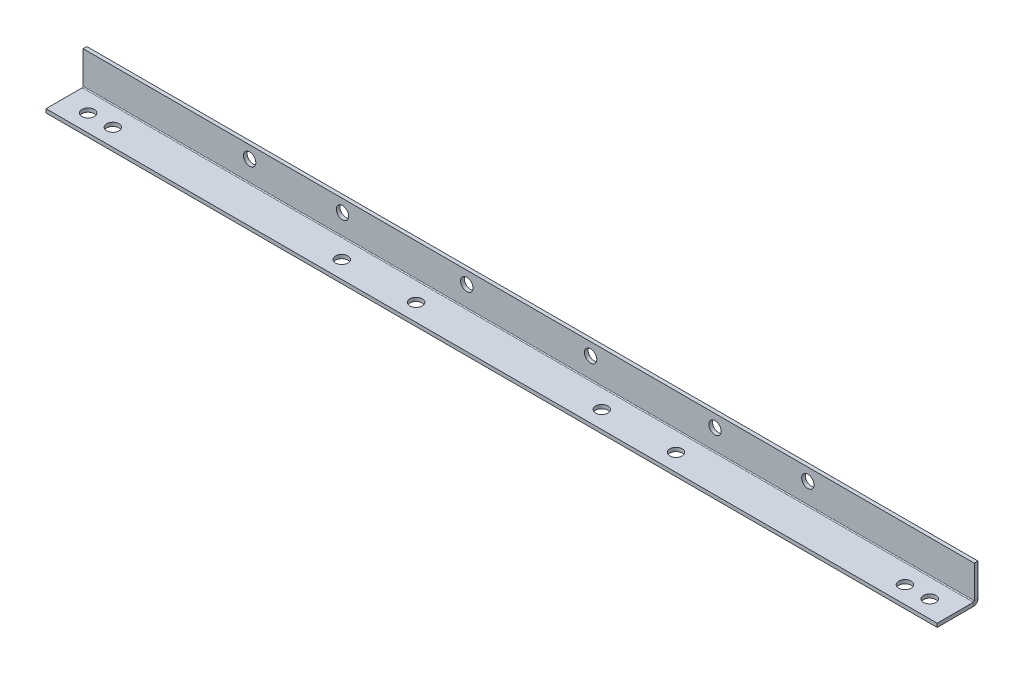
SolidWorks part; units mm, degrees
note: The reader was unsure of these and kept them because the rebuilt part matched: thickness of "Base-Flange1", "Edge-Flange1", "Sheet-Metal9", "Sheet-Metal10", "Sheet-Metal12", "Sheet-Metal13", "Sheet-Metal14", "Sheet-Metal15"; flange length of "Edge-Flange1".
material "6063-O"
ref_plane "Front Plane" through (0, 0, 0) normal (0, 0, 1) x (1, 0, 0)
ref_plane "Top Plane" through (0, 0, 0) normal (0, 1, 0) x (1, 0, 0)
ref_plane "Right Plane" through (0, 0, 0) normal (1, 0, 0) x (0, 0, -1)
sketch "Sketch2" plane through (0, 0, 0) normal (0, 1, 0) x (1, 0, 0)
  line L1 (-33.75, -275) -> (33.75, -275)
  line L2 (-33.75, -275) -> (-33.75, 275)
  line L3 (-33.75, 275) -> (33.75, 275)
  line L4 (33.75, -275) -> (33.75, 275)
  line L5 (-33.75, -275) -> (33.75, 275) construction
  line L6 (-33.75, 275) -> (33.75, -275) construction
  point P0 (0, 0)
sketch "Sketch3" plane through (0, 0, 0) normal (0, 1, 0) x (1, 0, 0)
  line L1 (-360, -15) -> (360, -15)
  line L2 (-360, -15) -> (-360, 15)
  line L3 (-360, 15) -> (360, 15)
  line L4 (360, -15) -> (360, 15)
  line L5 (-360, -15) -> (360, 15) construction
  line L6 (-360, 15) -> (360, -15) construction
  point P0 (0, 0)
  dimension "D1" = 720
  dimension "D2" = 30
base flange "Base-Flange1" sketch "Sketch3" thickness 3 reverse thickness direction no parameters "D1"=0.7366
edge flange "Edge-Flange1" sketch "Sketch8" flange angle 90 flange length 30 flange position material outside bend radius 0.7366 thickness 3 relief rectangular parameters "D6"=10
sketch "Sketch8" plane through (0, 0, -15) normal (0, 0, -1) x (-1, 0, 0)
  line L2 (-360, 0) -> (-360, 27)
  line L3 (-360, 27) -> (360, 27)
  line L4 (360, 27) -> (360, 0)
  line L11 (-360, 0) -> (360, 0) construction
  line L12 (-360, 0) -> (360, 0)
bend "EdgeBend1" bend radius 0.7366 bend angle 90 parameters "D5"=1
sketch "Sketch10" plane through (0, 0, 0) normal (0, 1, 0) x (1, 0, 0)
  line L0 (-360, 14.2634) -> (-360, -15) construction
  line L1 (-360, -15) -> (360, -15) construction
  circle A0 centre (-340, -1) radius 5
  circle A1 centre (-320, -1) radius 5
  dimension "D1" = 10
  dimension "D2" = 10
  dimension "D3" = 20
  dimension "D4" = 20
  dimension "D5" = 14
extrude "Cut-Extrude2" cut sketch "Sketch10" against normal blind 10 normal cut yes
mirror "Mirror1" about plane through (0, 0, 0) normal (1, 0, 0) of "Cut-Extrude2"
sketch "Sketch11" plane through (0, 0, -15) normal (0, 0, 1) x (1, 0, 0)
  line L0 (360, 27) -> (360, 0.7366) construction
  line L1 (-360, 0.7366) -> (-360, 27) construction
  line L2 (-360, 27) -> (360, 27) construction
  circle A0 centre (225.5, 17) radius 5
  circle A1 centre (-225.5, 17) radius 5
  circle A2 centre (-150.5, 17) radius 5
  circle A3 centre (150.5, 17) radius 5
  circle A4 centre (50, 17) radius 5
  circle A5 centre (-50, 17) radius 5
  point P18 (0, 27)
  dimension "D1" = 134.5
  dimension "D2" = 134.5
  dimension "D3" = 10
  dimension "D4" = 10
  dimension "D5" = 10
  dimension "D6" = 10
  dimension "D7" = 10
  dimension "D8" = 10
  dimension "D9" = 75
  dimension "D10" = 75
  dimension "D11" = 50
  dimension "D12" = 50
  dimension "D13" = 10
  dimension "D14" = 10
extrude "Cut-Extrude3" cut sketch "Sketch11" against normal blind 10 normal cut yes
sketch "Sketch12" plane through (0, 0, 0) normal (0, 1, 0) x (1, 0, 0)
  line L0 (-360, 18) -> (360, 18) construction
  circle A0 centre (-75, -1) radius 5
  circle A1 centre (75, -1) radius 5
  circle A2 centre (135, -1) radius 5
  circle A3 centre (-135, -1) radius 5
  point P10 (0, 18)
  dimension "D1" = 150
  dimension "D2" = 60
  dimension "D3" = 60
  dimension "D4" = 75
  dimension "D5" = 10
  dimension "D6" = 10
  dimension "D7" = 10
  dimension "D8" = 10
  dimension "D12" = 0
extrude "Cut-Extrude4" cut sketch "Sketch12" against normal blind 10 normal cut yes
sketch "Bend-Lines1" [suppressed] plane through (0, 0, 0) normal (0, 1, 0) x (1, 0, 0)
sketch "Bounding-Box1" [suppressed] plane through (0, 0, 0) normal (0, 1, 0) x (1, 0, 0)
sheet metal parameters "Sheet-Metal9" thickness 3 parameters "D1"=0.7366
flat pattern "Flat-Pattern9" [suppressed]
sketch "굽힘 선1" plane through (0, 0, 0) normal (0, 1, 0) x (1, 0, 0)
sketch3d "경계 상자1" [suppressed]
  line L0 (-360, 15, 0) -> (360, 15, 0) construction
  line L1 (-360, -15, 0) -> (360, -15, 0) construction
  line L2 (-360, 15, 0) -> (-360, -15, 0) construction
  line L3 (360, 15, 0) -> (360, -15, 0) construction
sheet metal parameters "Sheet-Metal10" thickness 3 parameters "D1"=0.7366
flat pattern "Flat-Pattern9"
sketch "굽힘 선1" plane through (0, 0, 0) normal (0, 1, 0) x (1, 0, 0)
  line L0 (360, 16.02) -> (-360, 16.02) construction
  line L1 (360, 16.02) -> (-360, 16.02) construction
sketch3d "경계 상자1" [suppressed]
  line L0 (360, 44.04, 0) -> (-360, 44.04, 0) construction
  line L1 (360, -15, 0) -> (-360, -15, 0) construction
  line L2 (360, 44.04, 0) -> (360, -15, 0) construction
  line L3 (-360, 44.04, 0) -> (-360, -15, 0) construction
bend of the flat pattern "Flatten-<EdgeBend1>1"
sheet metal parameters "Sheet-Metal12" thickness 3 parameters "D1"=0.7366
flat pattern "Flat-Pattern9"
sketch "굽힘 선1" plane through (0, 0, 0) normal (0, 1, 0) x (1, 0, 0)
  line L0 (360, 16.02) -> (-360, 16.02) construction
  line L1 (360, 16.02) -> (-360, 16.02) construction
sketch3d "경계 상자1" [suppressed]
  line L0 (360, 44.04, 0) -> (-360, 44.04, 0) construction
  line L1 (360, -15, 0) -> (-360, -15, 0) construction
  line L2 (360, 44.04, 0) -> (360, -15, 0) construction
  line L3 (-360, 44.04, 0) -> (-360, -15, 0) construction
bend of the flat pattern "Flatten-<EdgeBend1>1"
sheet metal parameters "Sheet-Metal13" thickness 3 parameters "D1"=0.7366
flat pattern "Flat-Pattern9"
sketch "굽힘 선1" plane through (0, 0, 0) normal (0, 1, 0) x (1, 0, 0)
  line L0 (360, 16.02) -> (-360, 16.02) construction
  line L1 (360, 16.02) -> (-360, 16.02) construction
sketch3d "경계 상자1" [suppressed]
  line L0 (360, 44.04, 0) -> (-360, 44.04, 0) construction
  line L1 (360, -15, 0) -> (-360, -15, 0) construction
  line L2 (360, 44.04, 0) -> (360, -15, 0) construction
  line L3 (-360, 44.04, 0) -> (-360, -15, 0) construction
bend of the flat pattern "Flatten-<EdgeBend1>1"
sheet metal parameters "Sheet-Metal14" thickness 3 parameters "D1"=0.7366
flat pattern "Flat-Pattern9"
sketch "굽힘 선1" plane through (0, 0, 0) normal (0, 1, 0) x (1, 0, 0)
  line L0 (360, 16.02) -> (-360, 16.02) construction
  line L1 (360, 16.02) -> (-360, 16.02) construction
sketch3d "경계 상자1" [suppressed]
  line L0 (360, 44.04, 0) -> (-360, 44.04, 0) construction
  line L1 (360, -15, 0) -> (-360, -15, 0) construction
  line L2 (360, 44.04, 0) -> (360, -15, 0) construction
  line L3 (-360, 44.04, 0) -> (-360, -15, 0) construction
bend of the flat pattern "Flatten-<EdgeBend1>1"
sheet metal parameters "Sheet-Metal15" thickness 3 parameters "D1"=0.7366
flat pattern "Flat-Pattern9"
sketch "굽힘 선1" plane through (0, 0, 0) normal (0, 1, 0) x (1, 0, 0)
  line L0 (360, 16.02) -> (-360, 16.02) construction
  line L1 (360, 16.02) -> (-360, 16.02) construction
sketch3d "경계 상자1" [suppressed]
  line L0 (360, 44.04, 0) -> (-360, 44.04, 0) construction
  line L1 (360, -15, 0) -> (-360, -15, 0) construction
  line L2 (360, 44.04, 0) -> (360, -15, 0) construction
  line L3 (-360, 44.04, 0) -> (-360, -15, 0) construction
bend of the flat pattern "Flatten-<EdgeBend1>1"
